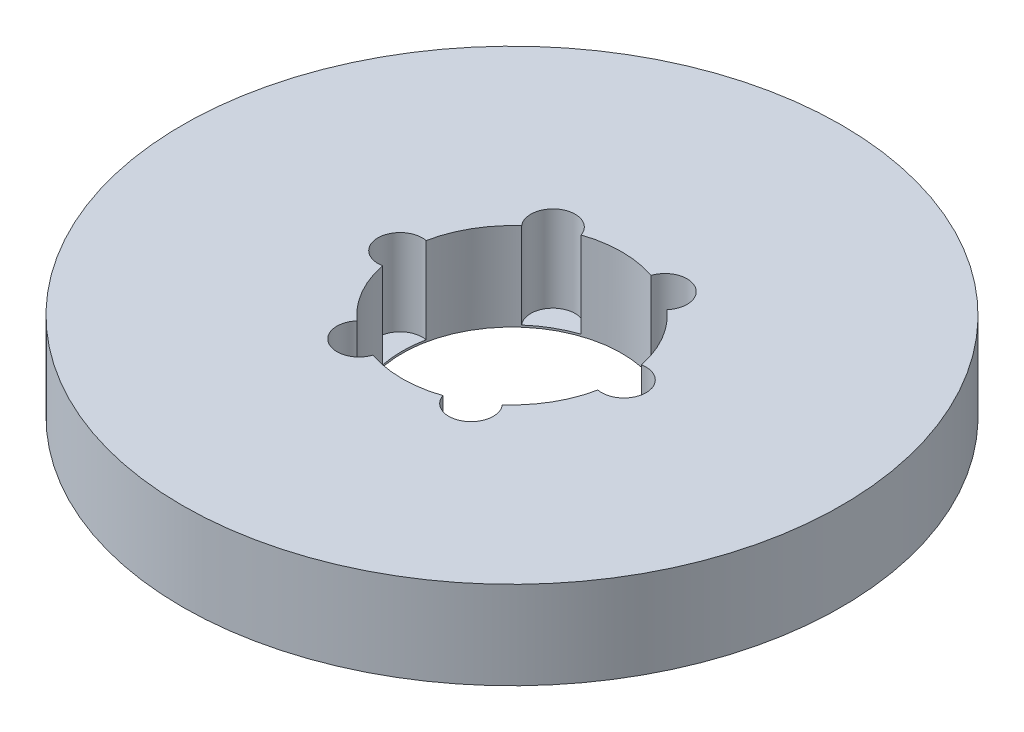
SolidWorks part; units mm, degrees
ref_plane "Front Plane" through (0, 0, 0) normal (0, 0, 1) x (1, 0, 0)
ref_plane "Top Plane" through (0, 0, 0) normal (0, 1, 0) x (1, 0, 0)
ref_plane "Right Plane" through (0, 0, 0) normal (1, 0, 0) x (0, 0, -1)
sketch "Sketch1" plane through (0, 0, 0) normal (0, 1, 0) x (1, 0, 0)
  circle A0 centre (0, 0) radius 22.5
  dimension "FLANGE_OD" = 45
extrude "Boss-Extrude1" add sketch "Sketch1" along normal blind 6
sketch "Sketch2" plane through (0, 0, 0) normal (0, 1, 0) x (1, 0, 0)
  circle A0 centre (0, 0) radius 7.5
  dimension "BORE_D" = 15
extrude "Cut-Extrude1" cut sketch "Sketch2" along normal through all
sketch "Sketch3" plane through (0, 6, 0) normal (0, 1, 0) x (1, 0, 0)
  circle A0 centre (0, 0) radius 7.641 construction
  circle A1 centre (-7.641, 0) radius 1.5153
  dimension "BOLT_D" = 3.0306
  dimension "BOLT_PCD" = 15.282
extrude "Cut-Extrude2" cut sketch "Sketch3" against normal blind 5.8703
pattern_circular "CirPattern1" count 6 over 360 about axis through (0, 0, 0) along (0, 1, 0) of "Cut-Extrude2"
